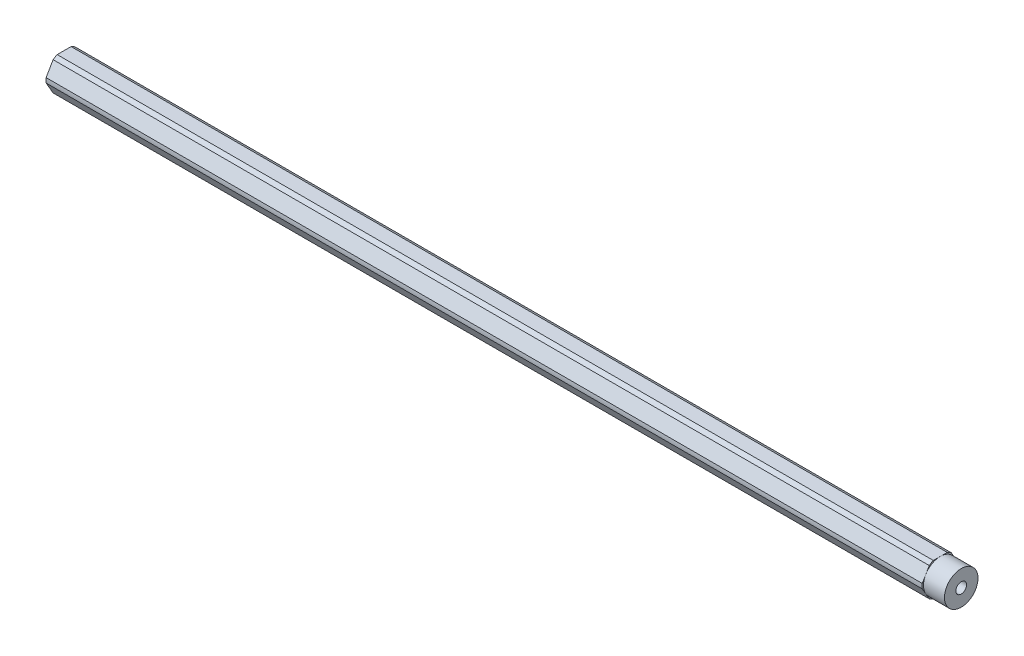
SolidWorks part; units mm, degrees
material "7075-T6 (SN)"
ref_plane "Front Plane" through (0, 0, 0) normal (0, 0, 1) x (1, 0, 0)
ref_plane "Top Plane" through (0, 0, 0) normal (0, 1, 0) x (1, 0, 0)
ref_plane "Right Plane" through (0, 0, 0) normal (1, 0, 0) x (0, 0, -1)
sketch "Sketch1" plane through (0, 0, 0) normal (1, 0, 0) x (0, 0, -1)
  line L1 (3.6662, 6.35) -> (-3.6662, 6.35)
  line L2 (-3.6662, 6.35) -> (-7.3323, 0)
  line L3 (-7.3323, 0) -> (-3.6662, -6.35)
  line L4 (-3.6662, -6.35) -> (3.6662, -6.35)
  line L5 (3.6662, -6.35) -> (7.3323, 0)
  line L6 (7.3323, 0) -> (3.6662, 6.35)
  circle A0 centre (0, 0) radius 6.875
  circle A1 centre (0, 0) radius 2.0193
  circle A2 centre (0, 0) radius 6.35 construction
  dimension "D1" = 12.7
  dimension "D2" = 13.75
  dimension "D3" = 4.0386
extrude "Boss-Extrude1" add sketch "Sketch1" along normal mid plane 339.725 contours L6 A0 L1 L2 L3 L4 L5 A1 region at (0, 5.7918, -3.3439)
hole_wizard "#10-32 Tapped Hole1" positions "3DSketch1" profile "Sketch2" tap size "#10-32" standard "ANSI Inch"
sketch3d "3DSketch1"
  circle A0 centre (-169.8625, 0, 0) radius 2.0193 construction
  circle A1 centre (169.8625, 0, 0) radius 2.0193 construction
  point P0 (169.8625, 0, 0)
  point P2 (-169.8625, 0, 0)
  point P7 (-167.8432, 0, 0)
  point P10 (171.8818, 0, 0)
sketch "Sketch2" plane through (169.8625, 0, 0) normal (0, 1, 0) x (0, 0, -1)
  line L0 (0, 0) -> (0, 17.5608)
  line L1 (0, 17.5608) -> (2.0193, 16.3474)
  line L2 (2.0193, 16.3474) -> (2.0193, 0)
  line L5 (2.0193, 0) -> (0, 0)
  line L10 (0, 17.5608) -> (-2.0193, 16.3474) construction
  line L11 (0, -6.35) -> (0, 107.95) construction
  dimension "Tap Drill Dia." = 4.0386
  dimension "Tap Drill Depth" = 16.3474
  dimension "Drill Angle" = 118
cosmetic thread "Hole Thread1" parameters "D1"=13.97, "D2"=4.826
cosmetic thread "Hole Thread2" parameters "D1"=13.97, "D2"=4.826
sketch "Sketch3" plane through (169.8625, 0, 0) normal (1, 0, 0) x (0, 0, -1)
  line L0 (6.8168, 0.893) -> (4.1818, 5.457) construction
  circle A0 centre (0, 0) radius 6.35
extrude "Cut-Extrude-Thin1" cut sketch "Sketch3" against normal blind 7.9375 thin thin type one direction wall 2.54
equation "\"D2@Sketch1\"=13.75mm"
